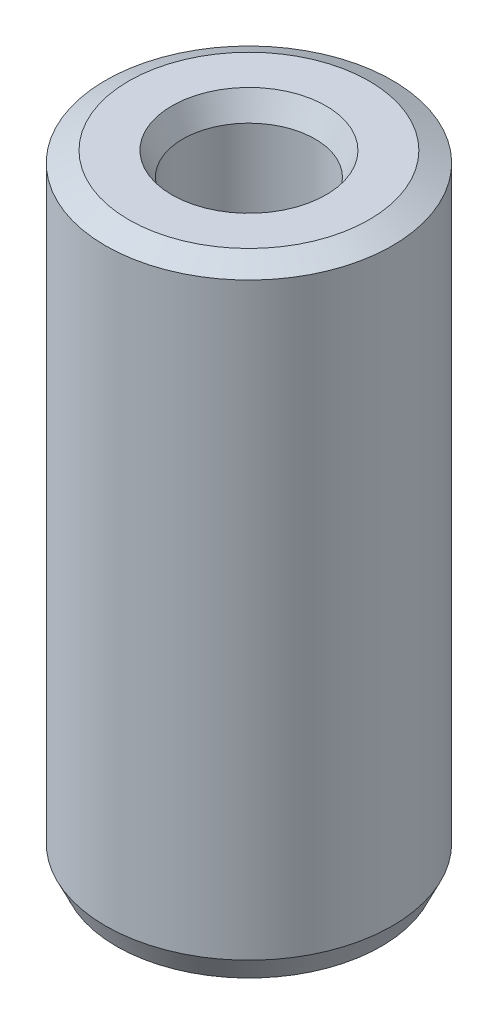
SolidWorks part; units mm, degrees
ref_plane "Front Plane" through (0, 0, 0) normal (0, 0, 1) x (1, 0, 0)
ref_plane "Top Plane" through (0, 0, 0) normal (0, 1, 0) x (1, 0, 0)
ref_plane "Right Plane" through (0, 0, 0) normal (1, 0, 0) x (0, 0, -1)
sketch "Sketch1" plane through (0, 0, 0) normal (0, 1, 0) x (1, 0, 0)
  circle A0 centre (0, 0) radius 40
  dimension "SLEEVE_OD" = 80
extrude "Boss-Extrude1" add sketch "Sketch1" along normal blind 173.8917
sketch "Sketch2" plane through (0, 0, 0) normal (0, 1, 0) x (1, 0, 0)
  circle A0 centre (0, 0) radius 18.4542
  dimension "BORE_D" = 36.9083
extrude "Cut-Extrude1" cut sketch "Sketch2" along normal through all
chamfer "Chamfer1" distance 3.0626 angle 64.659 4 edges at (0, 173.8917, 18.4542) (0, 0, 18.4542) (0, 0, 40) (0, 173.8917, 40) first distance on face at (0, 173.8917, 18.4542) first distance on face at (0, 0, 18.4542) first distance on face at (0, 173.8917, 40)
